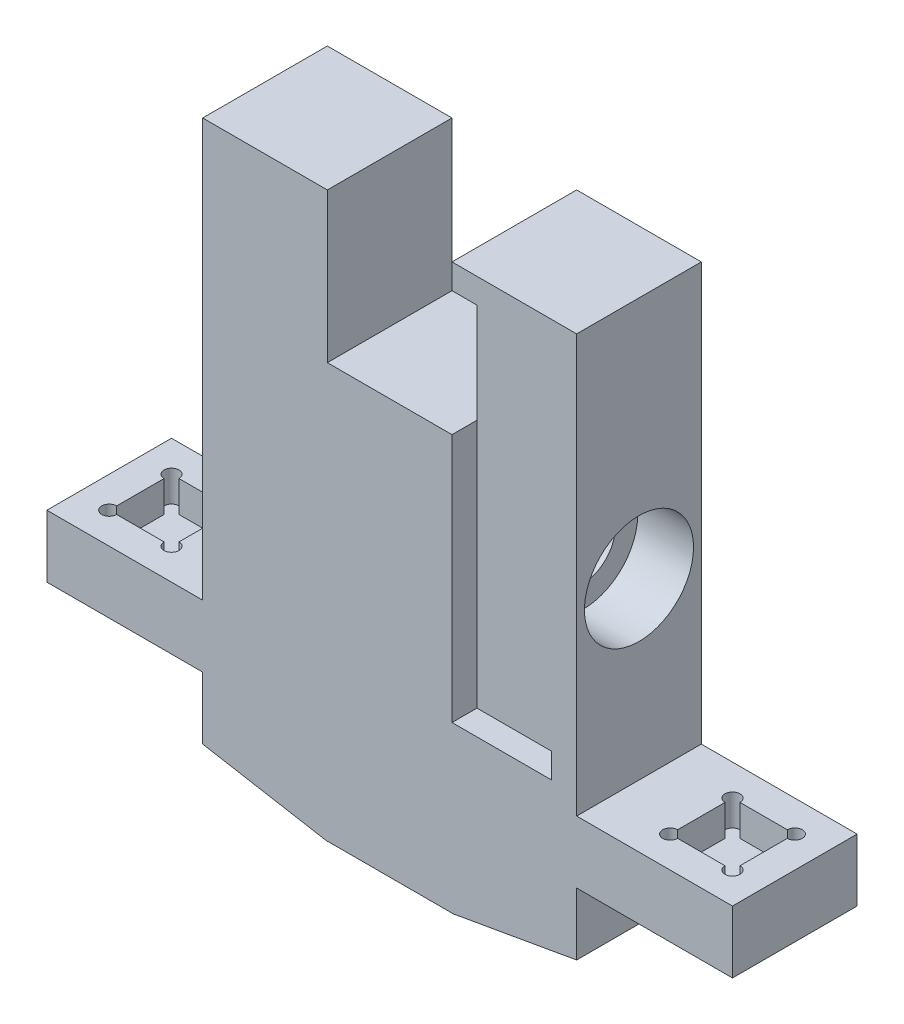
SolidWorks part; units mm, degrees
material "6061 Alloy"
ref_plane "Front Plane" through (0, 0, 0) normal (0, 0, 1) x (1, 0, 0)
ref_plane "Top Plane" through (0, 0, 0) normal (0, 1, 0) x (1, 0, 0)
ref_plane "Right Plane" through (0, 0, 0) normal (1, 0, 0) x (0, 0, -1)
sketch "Sketch2" plane through (0, 0, 0) normal (0, 0, 1) x (1, 0, 0)
  line L1 (-9.525, -15.875) -> (9.525, -15.875)
  line L2 (-9.525, -15.875) -> (-9.525, 15.875)
  line L3 (-9.525, 15.875) -> (9.525, 15.875)
  line L4 (9.525, -15.875) -> (9.525, 15.875)
  line L5 (-9.525, -15.875) -> (9.525, 15.875) construction
  line L6 (-9.525, 15.875) -> (9.525, -15.875) construction
  point P0 (0, 0)
  dimension "D1" = 31.75
  dimension "D2" = 19.05
extrude "Boss-Extrude1" add sketch "Sketch2" along normal mid plane 6.35
sketch "Sketch4" plane through (-1.5069, 3.1105, 3.175) normal (0, 0, 1) x (1, 0, 0)
  line L1 (-1.6681, 12.7645) -> (4.6819, 12.7645)
  line L2 (-1.6681, 12.7645) -> (-1.6681, 2.6045)
  line L3 (-1.6681, 2.6045) -> (4.6819, 2.6045)
  line L4 (4.6819, 12.7645) -> (4.6819, 2.6045)
  line L7 (-8.0181, 12.7645) -> (11.0319, 12.7645)
  line L8 (-8.0181, 12.7645) -> (-8.0181, 10.2245)
  line L9 (-8.0181, 10.2245) -> (11.0319, 10.2245)
  line L10 (11.0319, 12.7645) -> (11.0319, 10.2245)
  line L11 (11.0319, 12.7645) -> (-8.0181, 12.7645) construction
  line L12 (11.0319, -18.9855) -> (11.0319, 12.7645) construction
  line L13 (-8.0181, 12.7645) -> (-8.0181, -18.9855) construction
  dimension "D1" = 6.35
  dimension "D2" = 0
  dimension "D3" = 10.16
  dimension "D4" = 2.54
  dimension "D5" = 0
  dimension "D6" = 0
  dimension "D7" = 0
  dimension "D8" = 6.35
extrude "Cut-Extrude1" cut sketch "Sketch4" against normal through all contours L4 L9 | L2 L9 L4 | L9 L2 L3 L4 | L9 L2 region at (0, 14.605, 3.175) region at (-6.35, 14.605, 3.175) region at (6.35, 14.605, 3.175) region at (0, 9.525, 3.175)
sketch "Sketch6" plane through (-1.5069, 3.1105, 3.175) normal (0, 0, 1) x (1, 0, 0)
  line L0 (4.6819, 10.2245) -> (4.6819, 2.6045) construction
  line L5 (4.6819, 8.9545) -> (5.9519, 8.9545)
  line L6 (4.6819, 8.9545) -> (4.6819, -10.0955)
  line L7 (4.6819, -10.0955) -> (5.9519, -10.0955)
  line L8 (5.9519, 8.9545) -> (5.9519, -10.0955)
  line L12 (4.6819, -10.0955) -> (9.7619, -10.0955)
  line L13 (4.6819, -10.0955) -> (4.6819, -8.8255)
  line L14 (4.6819, -8.8255) -> (9.7619, -8.8255)
  line L15 (9.7619, -10.0955) -> (9.7619, -8.8255)
  line L16 (4.6819, 10.2245) -> (11.0319, 10.2245) construction
  line L17 (-8.0181, -18.9855) -> (11.0319, -18.9855) construction
  line L18 (11.0319, -18.9855) -> (11.0319, 10.2245) construction
  point P7 (5.3169, -10.0955)
  dimension "D1" = 1.27
  dimension "D2" = 1.27
  dimension "D3" = 8.89
  dimension "D4" = 1.27
  dimension "D5" = 1.27
extrude "Cut-Extrude2" cut sketch "Sketch6" against normal through all contours L6 L14 L8 L5 | L14 L6 L7 L8 | L12 L15 L14 L8 region at (3.81, 3.175, 3.175) region at (3.81, -6.35, 3.175) region at (6.35, -6.35, 3.175)
sketch "Sketch7" plane through (0, 0, 3.175) normal (0, 0, 1) x (1, 0, 0)
  line L0 (-9.525, -14.2875) -> (-0.5218, -15.875)
  line L1 (-9.525, 13.335) -> (-9.525, -15.875) construction
  line L2 (-9.525, -15.875) -> (9.525, -15.875) construction
  line L3 (-0.5218, -15.875) -> (-9.525, -15.875)
  line L4 (-9.525, -15.875) -> (-9.525, -14.2875)
  dimension "D1" = 1.5875
  dimension "D2" = 80
extrude "Cut-Extrude3" cut sketch "Sketch7" against normal through all
mirror "Mirror1" about plane through (0, 0, 0) normal (1, 0, 0) of "Cut-Extrude3"
sketch "Sketch8" plane through (0, 0, 3.175) normal (0, 0, 1) x (1, 0, 0)
  line L0 (-9.525, 13.335) -> (-9.525, -14.2875) construction
  line L1 (-9.525, -7.9375) -> (-17.4625, -7.9375)
  line L2 (-9.525, -7.9375) -> (-9.525, -11.1125)
  line L3 (-9.525, -11.1125) -> (-17.4625, -11.1125)
  line L4 (-17.4625, -7.9375) -> (-17.4625, -11.1125)
  dimension "D1" = 7.9375
  dimension "D2" = 3.175
  dimension "D3" = 3.175
extrude "Boss-Extrude2" add sketch "Sketch8" against normal blind 6.35
mirror "Mirror3" about plane through (0, 0, 0) normal (1, 0, 0) of "Boss-Extrude2"
sketch "Sketch9" plane through (0, 0, 3.175) normal (0, 0, 1) x (1, 0, 0)
  line L1 (-3.175, -15.3931) -> (3.175, -15.3931)
  line L2 (-3.175, -15.3931) -> (-3.175, -16.6935)
  line L3 (-3.175, -16.6935) -> (3.175, -16.6935)
  line L4 (3.175, -15.3931) -> (3.175, -16.6935)
  line L5 (-3.175, -15.3931) -> (3.175, -16.6935) construction
  line L6 (-3.175, -16.6935) -> (3.175, -15.3931) construction
  point P0 (0, -16.0433)
  dimension "D1" = 6.35
  dimension "D2" = 3.175
extrude "Cut-Extrude4" cut sketch "Sketch9" against normal through all
sketch "Sketch10" plane through (0, -7.9375, 0) normal (0, 1, 0) x (1, 0, 0)
  line L0 (-9.525, -3.175) -> (-17.4625, -3.175) construction
  line L1 (-12.7, -1.5875) -> (-15.875, -1.5875)
  line L2 (-12.7, -1.5875) -> (-12.7, 1.5875)
  line L3 (-12.7, 1.5875) -> (-15.875, 1.5875)
  line L4 (-15.875, -1.5875) -> (-15.875, 1.5875)
  line L5 (-12.7, -1.5875) -> (-15.875, 1.5875) construction
  line L6 (-12.7, 1.5875) -> (-15.875, -1.5875) construction
  line L8 (-17.4625, 3.175) -> (-17.4625, -3.175) construction
  circle A0 centre (-15.875, 1.5875) radius 0.381
  circle A1 centre (-12.7, 1.5875) radius 0.381
  circle A2 centre (-12.7, -1.5875) radius 0.381
  circle A3 centre (-15.875, -1.5875) radius 0.381
  point P0 (-14.2875, 0)
  dimension "D4" = 0.762
  dimension "D5" = 0.762
  dimension "D6" = 0.762
  dimension "D1" = 3.175
  dimension "D2" = 1.5875
  dimension "D3" = 1.5875
extrude "Cut-Extrude5" cut sketch "Sketch10" against normal blind 1.5875 contours A3 L1 A2 L2 A1 L3 A0 L4 | L4 A3 L1 | L1 A3 L4 | L2 A2 L1 | L1 A2 L2 | L3 A1 L2 | L2 A1 L3 | L4 A0 L3 | L3 A0 L4 region at (-15.9289, -7.9375, 1.6414) region at (-14.2875, -7.9375, 0) region at (-15.7133, -7.9375, 1.4258) region at (-12.8617, -7.9375, 1.4258) region at (-12.6461, -7.9375, 1.6414) region at (-15.9289, -7.9375, -1.6414) region at (-15.7133, -7.9375, -1.4258) region at (-12.8617, -7.9375, -1.4258) region at (-12.6461, -7.9375, -1.6414)
mirror "Mirror4" about plane through (0, 0, 0) normal (1, 0, 0) of "Cut-Extrude5"
hole_wizard "#6-32 Tapped Hole1" positions "Sketch13" profile "Sketch14" tap size "#6-32" standard "ANSI Inch"
sketch "Sketch13" plane through (0, -15.3931, 0) normal (0, -1, 0) x (-1, 0, 0)
  line L0 (3.175, 3.175) -> (3.175, -3.175) construction
  line L1 (3.175, -3.175) -> (9.525, -3.175) construction
  line L2 (-3.175, -3.175) -> (-9.525, -3.175) construction
  line L3 (-3.175, 3.175) -> (-3.175, -3.175) construction
  point P0 (6.35, 0)
  point P2 (-6.35, 0)
  dimension "D1" = 3.175
  dimension "D2" = 3.175
  dimension "D3" = 3.175
  dimension "D4" = 3.175
cosmetic thread "Hole Thread4" parameters "D1"=7.112, "D2"=3.5052
sketch "Sketch14" plane through (-6.35, -15.3931, 0) normal (1, 0, 0) x (0, 0, -1)
  line L0 (0, 0) -> (0, 10.2107)
  line L1 (0, 10.2107) -> (1.3525, 9.398)
  line L2 (1.3525, 9.398) -> (1.3525, 0)
  line L5 (1.3525, 0) -> (0, 0)
  line L10 (0, 10.2107) -> (-1.3526, 9.398) construction
  line L11 (0, -6.35) -> (0, 107.95) construction
  dimension "Tap Drill Dia." = 2.7051
  dimension "Tap Drill Depth" = 9.398
  dimension "Drill Angle" = 118
cosmetic thread "Hole Thread6" parameters "D1"=7.112, "D2"=3.5052
hole_wizard "CBORE for #4 Socket Head Cap Screw1" positions "Sketch15" profile "Sketch16" counterbore size "#4" standard "ANSI Inch" end condition up to next
sketch "Sketch15" plane through (9.525, 0, 0) normal (1, 0, 0) x (0, 0, -1)
  line L1 (3.175, -7.9375) -> (3.175, 13.335) construction
  point P8 (0, 0.9525)
  dimension "D1" = 4.7625
  dimension "D2" = 3.175
sketch "Sketch16" plane through (9.525, 0.9525, 0) normal (0, 1, 0) x (0, 0, -1)
  line L0 (0, 0) -> (0, 5.08)
  line L1 (0, 5.08) -> (1.6319, 5.08)
  line L3 (1.6319, 5.08) -> (1.6319, 2.8448)
  line L4 (1.6319, 2.8448) -> (2.7788, 2.8448)
  line L5 (2.7788, 2.8448) -> (2.7788, 0)
  line L7 (2.7788, 0) -> (0, 0)
  line L11 (0, -6.35) -> (0, 107.95) construction
  dimension "Thru Hole Dia." = 3.2639
  dimension "Thru Hole Depth" = 5.08
  dimension "C'Bore Dia." = 5.5575
  dimension "C'Bore Depth" = 2.8448
hole_wizard "#4-40 Tapped Hole1" positions "Sketch17" profile "Sketch19" tap size "#4-40" standard "ANSI Inch" end condition through all
sketch "Sketch17" plane through (3.175, 0, 0) normal (1, 0, 0) x (0, 0, -1)
  line L0 (3.175, 5.715) -> (-3.175, 5.715) construction
  line L1 (-3.175, 5.715) -> (-3.175, -6.985) construction
  point P0 (0, 0.9525)
  dimension "D1" = 4.7625
  dimension "D2" = 3.175
sketch "Sketch19" plane through (3.175, 0.9525, 0) normal (0, 1, 0) x (0, 0, -1)
  line L0 (0, 0) -> (0, 20.6375)
  line L1 (0, 20.6375) -> (1.1303, 20.6375)
  line L2 (1.1303, 20.6375) -> (1.1303, 0)
  line L5 (1.1303, 0) -> (0, 0)
  line L11 (0, -6.35) -> (0, 107.95) construction
  dimension "Thru Tap Drill Dia." = 2.2606
  dimension "Thru Tap Drill Depth" = 20.6375
cosmetic thread "Hole Thread5" parameters "D2"=2.8448
